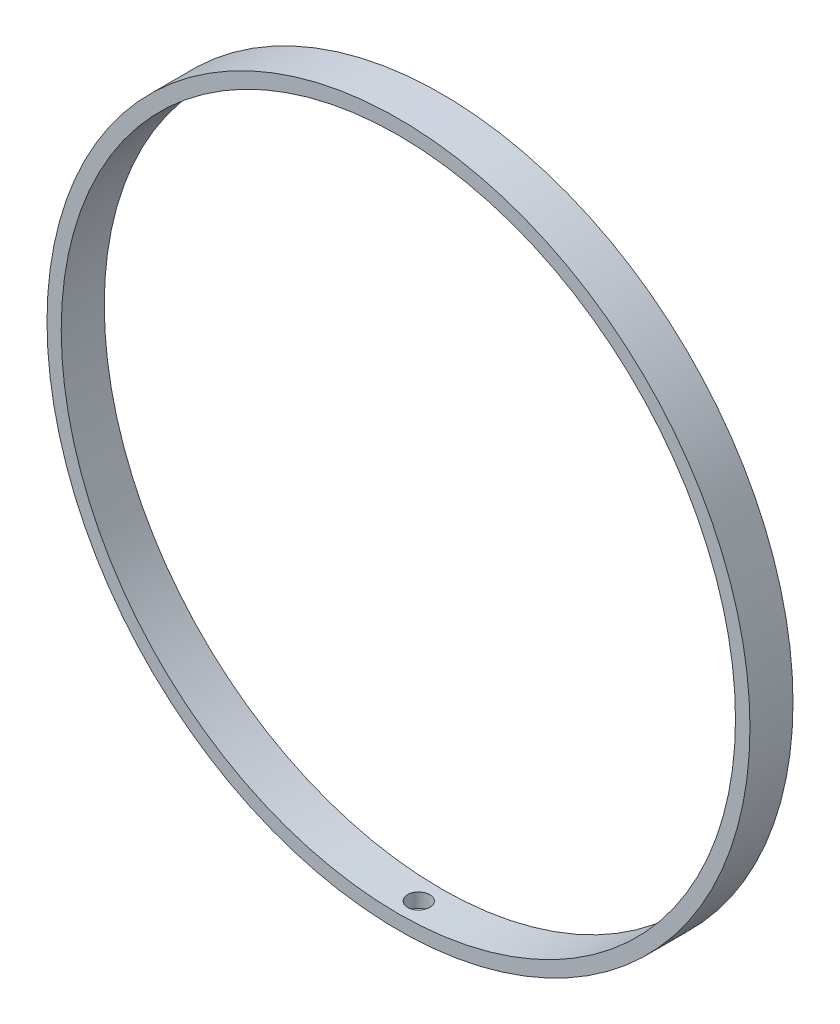
SolidWorks part; units mm, degrees
material "PVC rigide"
ref_plane "Plan de face" through (0, 0, 0) normal (0, 0, 1) x (1, 0, 0)
ref_plane "Plan de dessus" through (0, 0, 0) normal (0, 1, 0) x (1, 0, 0)
ref_plane "Plan de droite" through (0, 0, 0) normal (1, 0, 0) x (0, 0, -1)
sketch "Esquisse1" plane through (0, 0, 0) normal (0, 0, 1) x (1, 0, 0)
  circle A0 centre (-41.0074, 19.0392) radius 122.5
  dimension "D1" = 245
extrude "Boss.-Extru.1" add sketch "Esquisse1" along normal blind 15
sketch3d "Esquisse3D1"
  circle A0 centre (-41.0535, 19.0028, 0) radius 117.5
  point P2 (-41.0535, 19.0028, 117.5)
extrude "Enlèv. mat.-Extru.1" cut sketch "Esquisse3D1" along direction (0, 0, 1) on the side of the normal blind 21 contours A0
sketch "Esquisse2" plane through (0, 0, 0) normal (0, 1, 0) x (1, 0, 0)
  line L2 (-41.3104, 0) -> (-41.3104, -15.2506) construction
  line L3 (81.4926, 0) -> (-163.5074, 0) construction
  circle A0 centre (-41.3104, -7.6253) radius 3.85
  dimension "D1" = 7.7
extrude "Enlèv. mat.-Extru.2" cut sketch "Esquisse2" against normal through all
